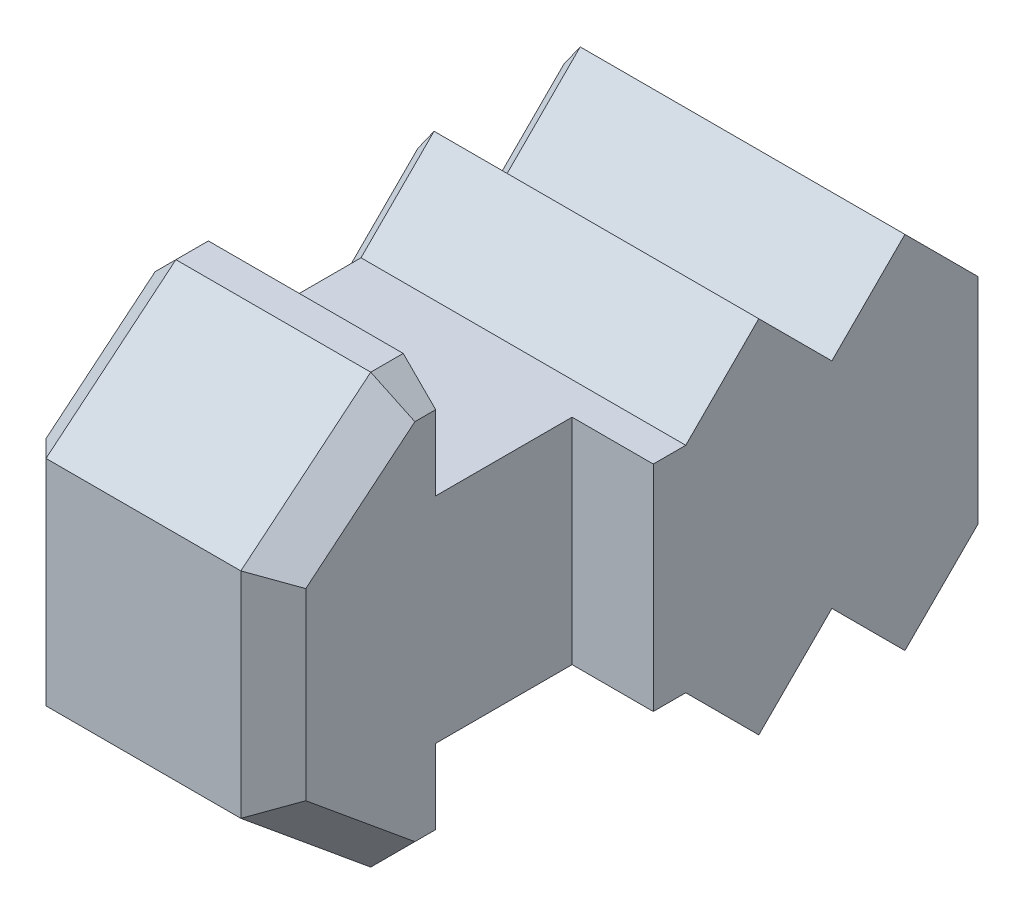
SolidWorks part; units mm, degrees
ref_plane "Front Plane" through (0, 0, 0) normal (1, 0, 0) x (0, 1, 0)
ref_plane "Top Plane" through (0, 0, 0) normal (0, 0, 1) x (0, 1, 0)
ref_plane "Right Plane" through (0, 0, 0) normal (0, 1, 0) x (-1, 0, 0)
sketch "Sketch1" plane through (0, 0, 0) normal (1, 0, 0) x (0, 1, 0)
  line L0 (0, 0) -> (0, 9.2) construction
  line L1 (-3.3, 9.2) -> (3.3, 9.2)
  line L2 (3.3, 9.2) -> (6.6, 5.2)
  line L3 (6.6, 5.2) -> (6.6, 4.2)
  line L4 (6.6, 4.2) -> (3.3, 4.2)
  line L5 (3.3, 4.2) -> (3.3, 0)
  line L6 (3.3, 0) -> (-3.3, 0) construction
  line L7 (6.6, 5.2) -> (6.6, 9.2) construction
  line L8 (6.6, 9.2) -> (3.3, 9.2) construction
  line L9 (-6.6, 5.2) -> (-6.6, 4.2)
  line L10 (-3.3, 9.2) -> (-6.6, 5.2)
  line L11 (-6.6, 4.2) -> (-3.3, 4.2)
  line L12 (-3.3, 4.2) -> (-3.3, 0)
  line L16 (5.55, -7.75) -> (3.3, -5.5)
  line L18 (5.55, -7.75) -> (3.3, -10)
  line L19 (0, 0) -> (0, -10) construction
  line L20 (-3.3, -10) -> (3.3, -10)
  line L21 (3.3, -5.5) -> (5.55, -3.25)
  line L22 (3.3, -5.5) -> (3.3, -10) construction
  line L28 (5.55, -3.25) -> (3.3, -1)
  line L29 (3.3, -5.5) -> (3.3, -1) construction
  line L30 (5.55, -7.75) -> (5.55, -3.25) construction
  line L31 (3.3, -1) -> (3.3, 0)
  line L32 (3.3, -10) -> (5.55, -10) construction
  line L33 (5.55, -10) -> (5.55, -7.75) construction
  line L34 (5.55, -7.75) -> (3.3, -7.75) construction
  line L35 (5.55, -3.25) -> (3.3, -3.25) construction
  line L36 (3.3, -5.5) -> (5.55, -5.5) construction
  line L37 (-5.55, -3.25) -> (-3.3, -1)
  line L38 (-3.3, -5.5) -> (-5.55, -3.25)
  line L39 (-5.55, -7.75) -> (-3.3, -5.5)
  line L40 (-5.55, -7.75) -> (-3.3, -10)
  line L41 (-3.3, -1) -> (-3.3, 0)
  dimension "D1" = 3.3
  dimension "D2" = 1
  dimension "D3" = 4
  dimension "D4" = 4.2
  dimension "D5" = 3.3
  dimension "D9" = 10
  dimension "D11" = 1
  dimension "D6" = 45
  dimension "D7" = 45
  dimension "D8" = 45
  dimension "D10" = 45
extrude "Boss-Extrude1" add sketch "Sketch1" along normal blind 4 and the other way blind 4
sketch "Sketch2" plane through (4, 0, 0) normal (1, 0, 0) x (0, 1, 0)
  line L0 (-3.3, 0) -> (3.3, 0)
  line L20 (-5.55, -7.75) -> (-3.3, -10)
  line L21 (3.3, -10) -> (5.55, -7.75)
  line L22 (-3.3, -10) -> (3.3, -10)
  line L23 (-5.55, -7.75) -> (-3.3, -10)
  line L24 (-3.3, -5.5) -> (-5.55, -7.75)
  line L25 (-3.3, -5.5) -> (-5.55, -7.75)
  line L26 (-5.55, -3.25) -> (-3.3, -5.5)
  line L28 (-3.3, 4.2) -> (-3.3, 0)
  line L29 (-6.6, 4.2) -> (-3.3, 4.2)
  line L30 (-6.6, 5.2) -> (-6.6, 4.2)
  line L31 (-3.3, 9.2) -> (-6.6, 5.2)
  line L32 (3.3, 9.2) -> (-3.3, 9.2)
  line L33 (6.6, 5.2) -> (3.3, 9.2)
  line L34 (6.6, 4.2) -> (6.6, 5.2)
  line L35 (3.3, 4.2) -> (6.6, 4.2)
  line L36 (3.3, 0) -> (3.3, 4.2)
  line L38 (-5.55, -3.25) -> (-3.3, -5.5)
  line L39 (-3.3, -1) -> (-5.55, -3.25)
  line L41 (3.3, -10) -> (5.55, -7.75)
  line L42 (-3.3, -10) -> (3.3, -10)
  line L61 (-3.3, -1) -> (-5.55, -3.25)
  line L62 (-3.3, 0) -> (-3.3, -1)
  line L63 (-3.3, 0) -> (-3.3, -1)
  line L64 (3.3, -1) -> (3.3, 0)
  line L65 (3.3, -1) -> (3.3, 0)
  line L66 (5.55, -3.25) -> (3.3, -1)
  line L67 (5.55, -3.25) -> (3.3, -1)
  line L68 (3.3, -5.5) -> (5.55, -3.25)
  line L69 (3.3, -5.5) -> (5.55, -3.25)
  line L70 (5.55, -7.75) -> (3.3, -5.5)
  line L71 (5.55, -7.75) -> (3.3, -5.5)
  dimension "D1" = 0
extrude "Boss-Extrude2" add sketch "Sketch2" along normal blind 2.5
chamfer "Chamfer1" distance 1 angle 45 10 edges at (-4, 6.6, 4.7) (-4, 4.95, 7.2) (-4, 0, 9.2) (-4, -4.95, 7.2) (-4, -6.6, 4.7) (4, -6.6, 4.7) (4, -4.95, 7.2) (4, 0, 9.2) (4, 4.95, 7.2) (4, 6.6, 4.7)
sketch "Sketch3" plane through (-4, 0, 0) normal (-1, 0, 0) x (0, -1, 0)
  line L0 (0, 0) -> (0, -10) construction
  line L1 (3.3, -10) -> (-3.3, -10) construction
  line L2 (0, -8) -> (2, -10)
  line L3 (2, -10) -> (-2, -10)
  line L4 (0, -10) -> (0, -8) construction
  line L5 (0, -8) -> (-2, -10)
  dimension "D1" = 45
  dimension "D2" = 2
extrude "Cut-Extrude1" cut sketch "Sketch3" against normal offset from surface (8.5 mm away) 2 up to face at (6.5, 0, -4.5833)
chamfer "Chamfer2" distance 0.5 angle 45 14 edges at (-4, -3.3, 1.6) (-4, 3.3, 1.6) (-4, -2.65, -10) (-4, -1, -9) (-4, 1, -9) (-4, 2.65, -10) (-4, 4.425, -8.875) (-4, -4.425, -2.125) (-4, -4.425, -4.375) (-4, -4.425, -6.625) (-4, -4.425, -8.875) (-4, 4.425, -2.125) (-4, 4.425, -4.375) (-4, 4.425, -6.625)
equation "\"D7@Sketch1\"=\"D6@Sketch1\""
equation "\"D8@Sketch1\"=\"D6@Sketch1\""
equation "\"D10@Sketch1\"=\"D6@sketch1\""
